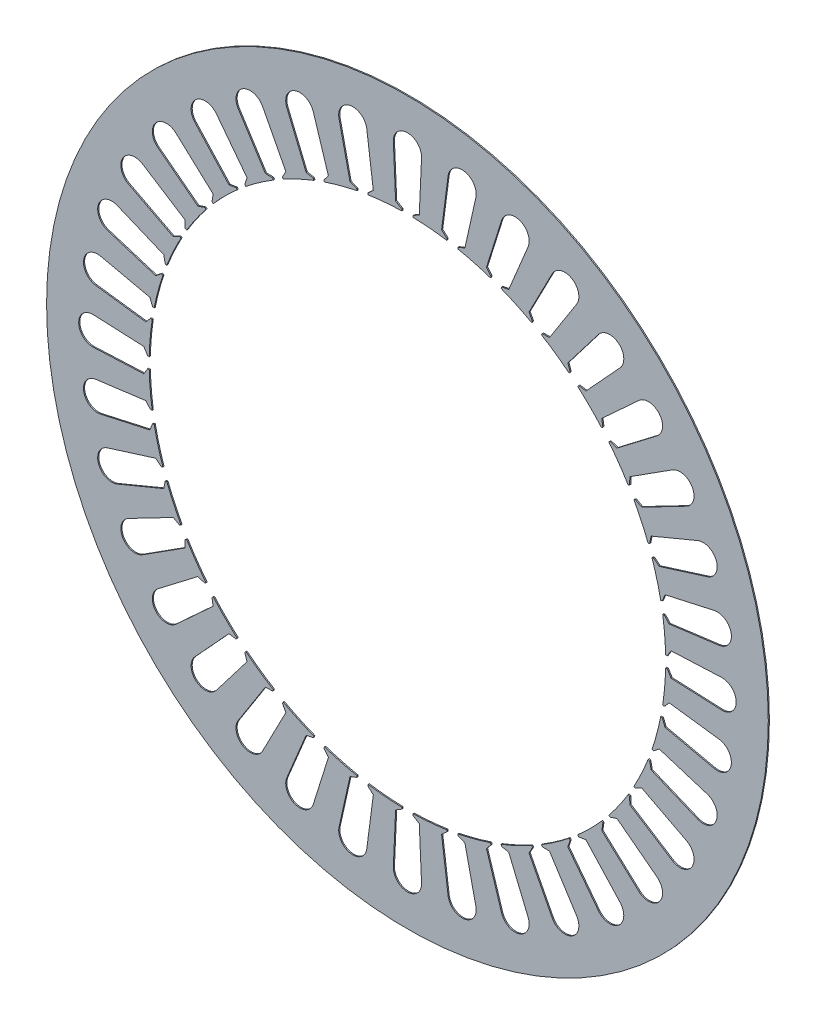
SolidWorks part; units mm, degrees
ref_plane "Front Plane" through (0, 0, 0) normal (0, 0, 1) x (1, 0, 0)
ref_plane "Top Plane" through (0, 0, 0) normal (0, 1, 0) x (1, 0, 0)
ref_plane "Right Plane" through (0, 0, 0) normal (1, 0, 0) x (0, 0, -1)
sketch "Stator sketch" plane through (0, 0, 0) normal (0, 0, 1) x (1, 0, 0)
  line L0 (0, 0) -> (0, 64) construction
  line L1 (2.0989, 46.7539) -> (2.5, 55.6878)
  line L2 (-2.0989, 46.7539) -> (-2.5, 55.6878)
  line L5 (-1.0066, 46.0891) -> (-2.0989, 46.7539)
  line L6 (-1, 45.7891) -> (-1.0066, 46.0891)
  line L7 (1.0066, 46.0891) -> (2.0989, 46.7539)
  line L8 (1, 45.7891) -> (1.0066, 46.0891)
  line L9 (6.9664, 45.2671) -> (7.012, 45.5637)
  line L10 (7.012, 45.5637) -> (6.0517, 46.4081)
  line L11 (6.0517, 46.4081) -> (7.2081, 55.2759)
  line L12 (8.936, 44.9198) -> (8.9945, 45.2141)
  line L13 (8.9945, 45.2141) -> (10.1858, 45.6791)
  line L14 (10.1858, 45.6791) -> (12.1321, 54.4076)
  line L15 (14.7211, 43.3697) -> (14.8175, 43.6538)
  line L16 (14.8175, 43.6538) -> (14.0184, 44.6522)
  line L17 (14.0184, 44.6522) -> (16.6971, 53.1844)
  line L18 (16.6005, 42.6856) -> (16.7092, 42.9653)
  line L19 (16.7092, 42.9653) -> (17.9631, 43.2164)
  line L20 (17.9631, 43.2164) -> (21.3956, 51.4743)
  line L21 (22.0285, 40.1545) -> (22.1728, 40.4176)
  line L22 (22.1728, 40.4176) -> (21.5592, 41.5395)
  line L23 (21.5592, 41.5395) -> (25.6788, 49.477)
  line L24 (23.7606, 39.1545) -> (23.9162, 39.411)
  line L25 (23.9162, 39.411) -> (25.1947, 39.4406)
  line L26 (25.1947, 39.4406) -> (30.0089, 46.977)
  line L27 (28.6666, 35.7193) -> (28.8544, 35.9533)
  line L28 (28.8544, 35.9533) -> (28.445, 37.1647)
  line L29 (28.445, 37.1647) -> (33.8803, 44.2663)
  line L30 (30.1987, 34.4337) -> (30.3966, 34.6593)
  line L31 (30.3966, 34.6593) -> (31.6607, 34.4664)
  line L32 (31.6607, 34.4664) -> (37.7105, 41.0523)
  line L33 (34.4337, 30.1987) -> (34.6593, 30.3966)
  line L34 (34.6593, 30.3966) -> (34.4664, 31.6607)
  line L35 (34.4664, 31.6607) -> (41.0523, 37.7105)
  line L36 (35.7193, 28.6666) -> (35.9533, 28.8544)
  line L37 (35.9533, 28.8544) -> (37.1647, 28.445)
  line L38 (37.1647, 28.445) -> (44.2663, 33.8803)
  line L39 (39.1545, 23.7606) -> (39.411, 23.9162)
  line L40 (39.411, 23.9162) -> (39.4406, 25.1947)
  line L41 (39.4406, 25.1947) -> (46.977, 30.0089)
  line L42 (40.1545, 22.0285) -> (40.4176, 22.1728)
  line L43 (40.4176, 22.1728) -> (41.5395, 21.5592)
  line L44 (41.5395, 21.5592) -> (49.477, 25.6788)
  line L45 (42.6856, 16.6005) -> (42.9653, 16.7092)
  line L46 (42.9653, 16.7092) -> (43.2164, 17.9631)
  line L47 (43.2164, 17.9631) -> (51.4743, 21.3956)
  line L48 (43.3697, 14.7211) -> (43.6538, 14.8175)
  line L49 (43.6538, 14.8175) -> (44.6522, 14.0184)
  line L50 (44.6522, 14.0184) -> (53.1844, 16.6971)
  line L51 (44.9198, 8.936) -> (45.2141, 8.9945)
  line L52 (45.2141, 8.9945) -> (45.6791, 10.1858)
  line L53 (45.6791, 10.1858) -> (54.4076, 12.1321)
  line L54 (45.2671, 6.9664) -> (45.5637, 7.012)
  line L55 (45.5637, 7.012) -> (46.4081, 6.0517)
  line L56 (46.4081, 6.0517) -> (55.2759, 7.2081)
  line L57 (45.7891, 1) -> (46.0891, 1.0066)
  line L58 (46.0891, 1.0066) -> (46.7539, 2.0989)
  line L59 (46.7539, 2.0989) -> (55.6878, 2.5)
  line L60 (45.7891, -1) -> (46.0891, -1.0066)
  line L61 (46.0891, -1.0066) -> (46.7539, -2.0989)
  line L62 (46.7539, -2.0989) -> (55.6878, -2.5)
  line L63 (45.2671, -6.9664) -> (45.5637, -7.012)
  line L64 (45.5637, -7.012) -> (46.4081, -6.0517)
  line L65 (46.4081, -6.0517) -> (55.2759, -7.2081)
  line L66 (44.9198, -8.936) -> (45.2141, -8.9945)
  line L67 (45.2141, -8.9945) -> (45.6791, -10.1858)
  line L68 (45.6791, -10.1858) -> (54.4076, -12.1321)
  line L69 (43.3697, -14.7211) -> (43.6538, -14.8175)
  line L70 (43.6538, -14.8175) -> (44.6522, -14.0184)
  line L71 (44.6522, -14.0184) -> (53.1844, -16.6971)
  line L72 (42.6856, -16.6005) -> (42.9653, -16.7092)
  line L73 (42.9653, -16.7092) -> (43.2164, -17.9631)
  line L74 (43.2164, -17.9631) -> (51.4743, -21.3956)
  line L75 (40.1545, -22.0285) -> (40.4176, -22.1728)
  line L76 (40.4176, -22.1728) -> (41.5395, -21.5592)
  line L77 (41.5395, -21.5592) -> (49.477, -25.6788)
  line L78 (39.1545, -23.7606) -> (39.411, -23.9162)
  line L79 (39.411, -23.9162) -> (39.4406, -25.1947)
  line L80 (39.4406, -25.1947) -> (46.977, -30.0089)
  line L81 (35.7193, -28.6666) -> (35.9533, -28.8544)
  line L82 (35.9533, -28.8544) -> (37.1647, -28.445)
  line L83 (37.1647, -28.445) -> (44.2663, -33.8803)
  line L84 (34.4337, -30.1987) -> (34.6593, -30.3966)
  line L85 (34.6593, -30.3966) -> (34.4664, -31.6607)
  line L86 (34.4664, -31.6607) -> (41.0523, -37.7105)
  line L87 (30.1987, -34.4337) -> (30.3966, -34.6593)
  line L88 (30.3966, -34.6593) -> (31.6607, -34.4664)
  line L89 (31.6607, -34.4664) -> (37.7105, -41.0523)
  line L90 (28.6666, -35.7193) -> (28.8544, -35.9533)
  line L91 (28.8544, -35.9533) -> (28.445, -37.1647)
  line L92 (28.445, -37.1647) -> (33.8803, -44.2663)
  line L93 (23.7606, -39.1545) -> (23.9162, -39.411)
  line L94 (23.9162, -39.411) -> (25.1947, -39.4406)
  line L95 (25.1947, -39.4406) -> (30.0089, -46.977)
  line L96 (22.0285, -40.1545) -> (22.1728, -40.4176)
  line L97 (22.1728, -40.4176) -> (21.5592, -41.5395)
  line L98 (21.5592, -41.5395) -> (25.6788, -49.477)
  line L99 (16.6005, -42.6856) -> (16.7092, -42.9653)
  line L100 (16.7092, -42.9653) -> (17.9631, -43.2164)
  line L101 (17.9631, -43.2164) -> (21.3956, -51.4743)
  line L102 (14.7211, -43.3697) -> (14.8175, -43.6538)
  line L103 (14.8175, -43.6538) -> (14.0184, -44.6522)
  line L104 (14.0184, -44.6522) -> (16.6971, -53.1844)
  line L105 (8.936, -44.9198) -> (8.9945, -45.2141)
  line L106 (8.9945, -45.2141) -> (10.1858, -45.6791)
  line L107 (10.1858, -45.6791) -> (12.1321, -54.4076)
  line L108 (6.9664, -45.2671) -> (7.012, -45.5637)
  line L109 (7.012, -45.5637) -> (6.0517, -46.4081)
  line L110 (6.0517, -46.4081) -> (7.2081, -55.2759)
  line L111 (1, -45.7891) -> (1.0066, -46.0891)
  line L112 (1.0066, -46.0891) -> (2.0989, -46.7539)
  line L113 (2.0989, -46.7539) -> (2.5, -55.6878)
  line L114 (-1, -45.7891) -> (-1.0066, -46.0891)
  line L115 (-1.0066, -46.0891) -> (-2.0989, -46.7539)
  line L116 (-2.0989, -46.7539) -> (-2.5, -55.6878)
  line L117 (-6.9664, -45.2671) -> (-7.012, -45.5637)
  line L118 (-7.012, -45.5637) -> (-6.0517, -46.4081)
  line L119 (-6.0517, -46.4081) -> (-7.2081, -55.2759)
  line L120 (-8.936, -44.9198) -> (-8.9945, -45.2141)
  line L121 (-8.9945, -45.2141) -> (-10.1858, -45.6791)
  line L122 (-10.1858, -45.6791) -> (-12.1321, -54.4076)
  line L123 (-14.7211, -43.3697) -> (-14.8175, -43.6538)
  line L124 (-14.8175, -43.6538) -> (-14.0184, -44.6522)
  line L125 (-14.0184, -44.6522) -> (-16.6971, -53.1844)
  line L126 (-16.6005, -42.6856) -> (-16.7092, -42.9653)
  line L127 (-16.7092, -42.9653) -> (-17.9631, -43.2164)
  line L128 (-17.9631, -43.2164) -> (-21.3956, -51.4743)
  line L129 (-22.0285, -40.1545) -> (-22.1728, -40.4176)
  line L130 (-22.1728, -40.4176) -> (-21.5592, -41.5395)
  line L131 (-21.5592, -41.5395) -> (-25.6788, -49.477)
  line L132 (-23.7606, -39.1545) -> (-23.9162, -39.411)
  line L133 (-23.9162, -39.411) -> (-25.1947, -39.4406)
  line L134 (-25.1947, -39.4406) -> (-30.0089, -46.977)
  line L135 (-28.6666, -35.7193) -> (-28.8544, -35.9533)
  line L136 (-28.8544, -35.9533) -> (-28.445, -37.1647)
  line L137 (-28.445, -37.1647) -> (-33.8803, -44.2663)
  line L138 (-30.1987, -34.4337) -> (-30.3966, -34.6593)
  line L139 (-30.3966, -34.6593) -> (-31.6607, -34.4664)
  line L140 (-31.6607, -34.4664) -> (-37.7105, -41.0523)
  line L141 (-34.4337, -30.1987) -> (-34.6593, -30.3966)
  line L142 (-34.6593, -30.3966) -> (-34.4664, -31.6607)
  line L143 (-34.4664, -31.6607) -> (-41.0523, -37.7105)
  line L144 (-35.7193, -28.6666) -> (-35.9533, -28.8544)
  line L145 (-35.9533, -28.8544) -> (-37.1647, -28.445)
  line L146 (-37.1647, -28.445) -> (-44.2663, -33.8803)
  line L147 (-39.1545, -23.7606) -> (-39.411, -23.9162)
  line L148 (-39.411, -23.9162) -> (-39.4406, -25.1947)
  line L149 (-39.4406, -25.1947) -> (-46.977, -30.0089)
  line L150 (-40.1545, -22.0285) -> (-40.4176, -22.1728)
  line L151 (-40.4176, -22.1728) -> (-41.5395, -21.5592)
  line L152 (-41.5395, -21.5592) -> (-49.477, -25.6788)
  line L153 (-42.6856, -16.6005) -> (-42.9653, -16.7092)
  line L154 (-42.9653, -16.7092) -> (-43.2164, -17.9631)
  line L155 (-43.2164, -17.9631) -> (-51.4743, -21.3956)
  line L156 (-43.3697, -14.7211) -> (-43.6538, -14.8175)
  line L157 (-43.6538, -14.8175) -> (-44.6522, -14.0184)
  line L158 (-44.6522, -14.0184) -> (-53.1844, -16.6971)
  line L159 (-44.9198, -8.936) -> (-45.2141, -8.9945)
  line L160 (-45.2141, -8.9945) -> (-45.6791, -10.1858)
  line L161 (-45.6791, -10.1858) -> (-54.4076, -12.1321)
  line L162 (-45.2671, -6.9664) -> (-45.5637, -7.012)
  line L163 (-45.5637, -7.012) -> (-46.4081, -6.0517)
  line L164 (-46.4081, -6.0517) -> (-55.2759, -7.2081)
  line L165 (-45.7891, -1) -> (-46.0891, -1.0066)
  line L166 (-46.0891, -1.0066) -> (-46.7539, -2.0989)
  line L167 (-46.7539, -2.0989) -> (-55.6878, -2.5)
  line L168 (-45.7891, 1) -> (-46.0891, 1.0066)
  line L169 (-46.0891, 1.0066) -> (-46.7539, 2.0989)
  line L170 (-46.7539, 2.0989) -> (-55.6878, 2.5)
  line L171 (-45.2671, 6.9664) -> (-45.5637, 7.012)
  line L172 (-45.5637, 7.012) -> (-46.4081, 6.0517)
  line L173 (-46.4081, 6.0517) -> (-55.2759, 7.2081)
  line L174 (-44.9198, 8.936) -> (-45.2141, 8.9945)
  line L175 (-45.2141, 8.9945) -> (-45.6791, 10.1858)
  line L176 (-45.6791, 10.1858) -> (-54.4076, 12.1321)
  line L177 (-43.3697, 14.7211) -> (-43.6538, 14.8175)
  line L178 (-43.6538, 14.8175) -> (-44.6522, 14.0184)
  line L179 (-44.6522, 14.0184) -> (-53.1844, 16.6971)
  line L180 (-42.6856, 16.6005) -> (-42.9653, 16.7092)
  line L181 (-42.9653, 16.7092) -> (-43.2164, 17.9631)
  line L182 (-43.2164, 17.9631) -> (-51.4743, 21.3956)
  line L183 (-40.1545, 22.0285) -> (-40.4176, 22.1728)
  line L184 (-40.4176, 22.1728) -> (-41.5395, 21.5592)
  line L185 (-41.5395, 21.5592) -> (-49.477, 25.6788)
  line L186 (-39.1545, 23.7606) -> (-39.411, 23.9162)
  line L187 (-39.411, 23.9162) -> (-39.4406, 25.1947)
  line L188 (-39.4406, 25.1947) -> (-46.977, 30.0089)
  line L189 (-35.7193, 28.6666) -> (-35.9533, 28.8544)
  line L190 (-35.9533, 28.8544) -> (-37.1647, 28.445)
  line L191 (-37.1647, 28.445) -> (-44.2663, 33.8803)
  line L192 (-34.4337, 30.1987) -> (-34.6593, 30.3966)
  line L193 (-34.6593, 30.3966) -> (-34.4664, 31.6607)
  line L194 (-34.4664, 31.6607) -> (-41.0523, 37.7105)
  line L195 (-30.1987, 34.4337) -> (-30.3966, 34.6593)
  line L196 (-30.3966, 34.6593) -> (-31.6607, 34.4664)
  line L197 (-31.6607, 34.4664) -> (-37.7105, 41.0523)
  line L198 (-28.6666, 35.7193) -> (-28.8544, 35.9533)
  line L199 (-28.8544, 35.9533) -> (-28.445, 37.1647)
  line L200 (-28.445, 37.1647) -> (-33.8803, 44.2663)
  line L201 (-23.7606, 39.1545) -> (-23.9162, 39.411)
  line L202 (-23.9162, 39.411) -> (-25.1947, 39.4406)
  line L203 (-25.1947, 39.4406) -> (-30.0089, 46.977)
  line L204 (-22.0285, 40.1545) -> (-22.1728, 40.4176)
  line L205 (-22.1728, 40.4176) -> (-21.5592, 41.5395)
  line L206 (-21.5592, 41.5395) -> (-25.6788, 49.477)
  line L207 (-16.6005, 42.6856) -> (-16.7092, 42.9653)
  line L208 (-16.7092, 42.9653) -> (-17.9631, 43.2164)
  line L209 (-17.9631, 43.2164) -> (-21.3956, 51.4743)
  line L210 (-14.7211, 43.3697) -> (-14.8175, 43.6538)
  line L211 (-14.8175, 43.6538) -> (-14.0184, 44.6522)
  line L212 (-14.0184, 44.6522) -> (-16.6971, 53.1844)
  line L213 (-8.936, 44.9198) -> (-8.9945, 45.2141)
  line L214 (-8.9945, 45.2141) -> (-10.1858, 45.6791)
  line L215 (-10.1858, 45.6791) -> (-12.1321, 54.4076)
  line L216 (-6.9664, 45.2671) -> (-7.012, 45.5637)
  line L217 (-7.012, 45.5637) -> (-6.0517, 46.4081)
  line L218 (-6.0517, 46.4081) -> (-7.2081, 55.2759)
  arc A0 (-1, 45.7891) -> (-6.9664, 45.2671) centre (0, 0) ccw
  circle A1 centre (0, 0) radius 64
  arc A2 (-2.5, 55.6878) -> (2.5, 55.6878) centre (0, 55.8) cw
  arc A3 (7.2081, 55.2759) -> (12.1321, 54.4076) centre (9.6896, 54.9523) cw
  arc A4 (16.6971, 53.1844) -> (21.3956, 51.4743) centre (19.0847, 52.4348) cw
  arc A5 (25.6788, 49.477) -> (30.0089, 46.977) centre (27.9, 48.3242) cw
  arc A6 (33.8803, 44.2663) -> (37.7105, 41.0523) centre (35.8675, 42.7453) cw
  arc A7 (41.0523, 37.7105) -> (44.2663, 33.8803) centre (42.7453, 35.8675) cw
  arc A8 (46.977, 30.0089) -> (49.477, 25.6788) centre (48.3242, 27.9) cw
  arc A9 (51.4743, 21.3956) -> (53.1844, 16.6971) centre (52.4348, 19.0847) cw
  arc A10 (54.4076, 12.1321) -> (55.2759, 7.2081) centre (54.9523, 9.6896) cw
  arc A11 (55.6878, 2.5) -> (55.6878, -2.5) centre (55.8, 0) cw
  arc A12 (55.2759, -7.2081) -> (54.4076, -12.1321) centre (54.9523, -9.6896) cw
  arc A13 (53.1844, -16.6971) -> (51.4743, -21.3956) centre (52.4348, -19.0847) cw
  arc A14 (49.477, -25.6788) -> (46.977, -30.0089) centre (48.3242, -27.9) cw
  arc A15 (44.2663, -33.8803) -> (41.0523, -37.7105) centre (42.7453, -35.8675) cw
  arc A16 (37.7105, -41.0523) -> (33.8803, -44.2663) centre (35.8675, -42.7453) cw
  arc A17 (30.0089, -46.977) -> (25.6788, -49.477) centre (27.9, -48.3242) cw
  arc A18 (21.3956, -51.4743) -> (16.6971, -53.1844) centre (19.0847, -52.4348) cw
  arc A19 (12.1321, -54.4076) -> (7.2081, -55.2759) centre (9.6896, -54.9523) cw
  arc A20 (2.5, -55.6878) -> (-2.5, -55.6878) centre (0, -55.8) cw
  arc A21 (-7.2081, -55.2759) -> (-12.1321, -54.4076) centre (-9.6896, -54.9523) cw
  arc A22 (-16.6971, -53.1844) -> (-21.3956, -51.4743) centre (-19.0847, -52.4348) cw
  arc A23 (-25.6788, -49.477) -> (-30.0089, -46.977) centre (-27.9, -48.3242) cw
  arc A24 (-33.8803, -44.2663) -> (-37.7105, -41.0523) centre (-35.8675, -42.7453) cw
  arc A25 (-41.0523, -37.7105) -> (-44.2663, -33.8803) centre (-42.7453, -35.8675) cw
  arc A26 (-46.977, -30.0089) -> (-49.477, -25.6788) centre (-48.3242, -27.9) cw
  arc A27 (-51.4743, -21.3956) -> (-53.1844, -16.6971) centre (-52.4348, -19.0847) cw
  arc A28 (-54.4076, -12.1321) -> (-55.2759, -7.2081) centre (-54.9523, -9.6896) cw
  arc A29 (-55.6878, -2.5) -> (-55.6878, 2.5) centre (-55.8, 0) cw
  arc A30 (-55.2759, 7.2081) -> (-54.4076, 12.1321) centre (-54.9523, 9.6896) cw
  arc A31 (-53.1844, 16.6971) -> (-51.4743, 21.3956) centre (-52.4348, 19.0847) cw
  arc A32 (-49.477, 25.6788) -> (-46.977, 30.0089) centre (-48.3242, 27.9) cw
  arc A33 (-44.2663, 33.8803) -> (-41.0523, 37.7105) centre (-42.7453, 35.8675) cw
  arc A34 (-37.7105, 41.0523) -> (-33.8803, 44.2663) centre (-35.8675, 42.7453) cw
  arc A35 (-30.0089, 46.977) -> (-25.6788, 49.477) centre (-27.9, 48.3242) cw
  arc A36 (-21.3956, 51.4743) -> (-16.6971, 53.1844) centre (-19.0847, 52.4348) cw
  arc A37 (-12.1321, 54.4076) -> (-7.2081, 55.2759) centre (-9.6896, 54.9523) cw
  arc A38 (-8.936, 44.9198) -> (-14.7211, 43.3697) centre (0, 0) ccw
  arc A39 (-16.6005, 42.6856) -> (-22.0285, 40.1545) centre (0, 0) ccw
  arc A40 (-23.7606, 39.1545) -> (-28.6666, 35.7193) centre (0, 0) ccw
  arc A41 (-30.1987, 34.4337) -> (-34.4337, 30.1987) centre (0, 0) ccw
  arc A42 (-35.7193, 28.6666) -> (-39.1545, 23.7606) centre (0, 0) ccw
  arc A43 (-40.1545, 22.0285) -> (-42.6856, 16.6005) centre (0, 0) ccw
  arc A44 (-43.3697, 14.7211) -> (-44.9198, 8.936) centre (0, 0) ccw
  arc A45 (-45.2671, 6.9664) -> (-45.7891, 1) centre (0, 0) ccw
  arc A46 (-45.7891, -1) -> (-45.2671, -6.9664) centre (0, 0) ccw
  arc A47 (-44.9198, -8.936) -> (-43.3697, -14.7211) centre (0, 0) ccw
  arc A48 (-42.6856, -16.6005) -> (-40.1545, -22.0285) centre (0, 0) ccw
  arc A49 (-39.1545, -23.7606) -> (-35.7193, -28.6666) centre (0, 0) ccw
  arc A50 (-34.4337, -30.1987) -> (-30.1987, -34.4337) centre (0, 0) ccw
  arc A51 (-28.6666, -35.7193) -> (-23.7606, -39.1545) centre (0, 0) ccw
  arc A52 (-22.0285, -40.1545) -> (-16.6005, -42.6856) centre (0, 0) ccw
  arc A53 (-14.7211, -43.3697) -> (-8.936, -44.9198) centre (0, 0) ccw
  arc A54 (-6.9664, -45.2671) -> (-1, -45.7891) centre (0, 0) ccw
  arc A55 (1, -45.7891) -> (6.9664, -45.2671) centre (0, 0) ccw
  arc A56 (8.936, -44.9198) -> (14.7211, -43.3697) centre (0, 0) ccw
  arc A57 (16.6005, -42.6856) -> (22.0285, -40.1545) centre (0, 0) ccw
  arc A58 (23.7606, -39.1545) -> (28.6666, -35.7193) centre (0, 0) ccw
  arc A59 (30.1987, -34.4337) -> (34.4337, -30.1987) centre (0, 0) ccw
  arc A60 (35.7193, -28.6666) -> (39.1545, -23.7606) centre (0, 0) ccw
  arc A61 (40.1545, -22.0285) -> (42.6856, -16.6005) centre (0, 0) ccw
  arc A62 (43.3697, -14.7211) -> (44.9198, -8.936) centre (0, 0) ccw
  arc A63 (45.2671, -6.9664) -> (45.7891, -1) centre (0, 0) ccw
  arc A64 (45.7891, 1) -> (45.2671, 6.9664) centre (0, 0) ccw
  arc A65 (44.9198, 8.936) -> (43.3697, 14.7211) centre (0, 0) ccw
  arc A66 (42.6856, 16.6005) -> (40.1545, 22.0285) centre (0, 0) ccw
  arc A67 (39.1545, 23.7606) -> (35.7193, 28.6666) centre (0, 0) ccw
  arc A68 (34.4337, 30.1987) -> (30.1987, 34.4337) centre (0, 0) ccw
  arc A69 (28.6666, 35.7193) -> (23.7606, 39.1545) centre (0, 0) ccw
  arc A70 (22.0285, 40.1545) -> (16.6005, 42.6856) centre (0, 0) ccw
  arc A71 (14.7211, 43.3697) -> (8.936, 44.9198) centre (0, 0) ccw
  arc A72 (6.9664, 45.2671) -> (1, 45.7891) centre (0, 0) ccw
  point P1 (-2.054, 45.7539)
  point P9 (-1, 45.7891)
  point P11 (-48.3576, -2.5936)
  point P13 (0, 45.8)
  point P15 (1, 45.7891)
  point P16 (0, 0)
  point P19 (0, 0)
  point P335 (0, 0)
  dimension "D1" = 91.6
  dimension "D2" = 128
  dimension "D3" = 5
  dimension "D4" = 10
  dimension "D5" = 2
  dimension "D6" = 1
  dimension "D7" = 0.3
  dimension "D8" = 36
extrude "Boss-Extrude1" add sketch "Stator sketch" along normal mid plane 0.2
equation "\"Inner diameter\"= 91.6mm"
equation "\"Slots\"= 36"
equation "\"Stator OD\"= 128mm"
equation "\"Slot width\"= 5mm"
equation "\"Slot depth\"= 10mm"
equation "\"Slot opening\"= 2mm"
equation "\"D1@Stator sketch\"=\"Inner diameter\""
equation "\"D2@Stator sketch\"=\"Stator OD\""
equation "\"D3@Stator sketch\"=\"Slot width\""
equation "\"D4@Stator sketch\"=\"Slot depth\""
equation "\"D5@Stator sketch\"=\"Slot opening\""
equation "\"Lamination thickness\"= 0.2mm"
equation "\"D1@Boss-Extrude1\"=\"Lamination thickness\""
